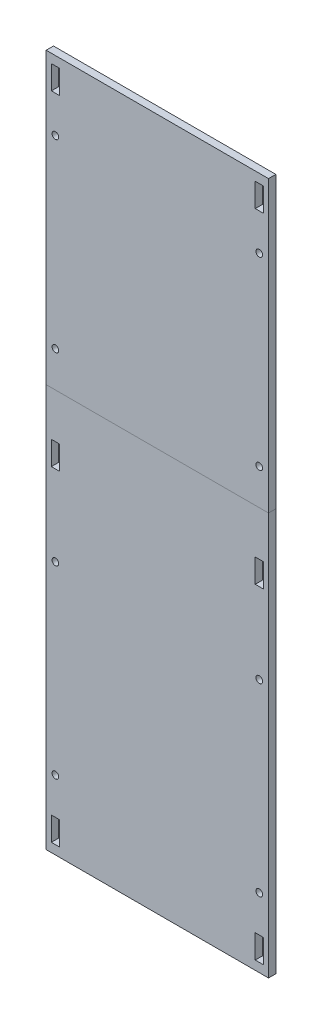
SolidWorks part; units mm, degrees
ref_plane "Front Plane" through (0, 0, 0) normal (0, 0, 1) x (1, 0, 0)
ref_plane "Top Plane" through (0, 0, 0) normal (0, 1, 0) x (1, 0, 0)
ref_plane "Right Plane" through (0, 0, 0) normal (1, 0, 0) x (0, 0, -1)
sketch "Sketch1" plane through (0, 0, 0) normal (0, 0, 1) x (1, 0, 0)
  line L2 (-44.17, -150) -> (-44.17, 150) construction
  line L4 (44.17, -150) -> (44.17, 150) construction
  line L5 (-44.17, -150) -> (44.17, 150) construction
  line L6 (-44.17, 150) -> (44.17, -150) construction
  line L7 (-48.17, -150) -> (48.17, -150)
  line L8 (-48.17, -150) -> (-48.17, 150)
  line L9 (-48.17, 150) -> (48.17, 150)
  line L10 (48.17, -150) -> (48.17, 150)
  line L11 (-48.17, -150) -> (48.17, 150) construction
  line L12 (-48.17, 150) -> (48.17, -150) construction
  line L13 (-45.9162, 135.875) -> (-42.4237, 135.875)
  line L14 (-45.9162, 135.875) -> (-45.9162, 146.125)
  line L15 (-45.9162, 146.125) -> (-42.4237, 146.125)
  line L16 (-42.4237, 135.875) -> (-42.4237, 146.125)
  line L17 (-45.9162, 135.875) -> (-42.4237, 146.125) construction
  line L18 (-45.9162, 146.125) -> (-42.4237, 135.875) construction
  line L19 (-45.9162, -5.125) -> (-42.4237, -5.125)
  line L20 (-45.9162, -5.125) -> (-45.9162, 5.125)
  line L21 (-45.9162, 5.125) -> (-42.4237, 5.125)
  line L22 (-42.4237, -5.125) -> (-42.4237, 5.125)
  line L23 (-45.9162, -5.125) -> (-42.4237, 5.125) construction
  line L24 (-45.9162, 5.125) -> (-42.4237, -5.125) construction
  line L25 (-45.9162, -146.125) -> (-42.4237, -146.125)
  line L26 (-45.9162, -146.125) -> (-45.9162, -135.875)
  line L27 (-45.9162, -135.875) -> (-42.4237, -135.875)
  line L28 (-42.4237, -146.125) -> (-42.4237, -135.875)
  line L29 (-45.9162, -146.125) -> (-42.4237, -135.875) construction
  line L30 (-45.9162, -135.875) -> (-42.4237, -146.125) construction
  circle A0 centre (-44.17, 120) radius 2.5 construction
  circle A1 centre (44.17, 120) radius 2.5 construction
  point P0 (0, 0)
  point P10 (-44.17, 141)
  point P12 (0, 0)
  point P20 (-44.17, 0)
  point P25 (-44.17, -141)
  dimension "D3" = 30
  dimension "D4" = 5
  dimension "D5" = 4
  dimension "D1" = 88.34
  dimension "D2" = 300
  dimension "D6" = 3.4925
  dimension "D7" = 10.25
  dimension "D8" = 9
  dimension "D9" = 9
extrude "Boss-Extrude1" add sketch "Sketch1" along normal mid plane 3.175 contours L9 L10 L7 L8
extrude "Cut-Extrude1" cut sketch "Sketch1<3>" against normal through all both and the other way through all contours L13 L16 L15 L14 | L19 L22 L21 L20 | L25 L28 L27 L26 region at (-44.17, 141, 0) region at (-44.17, 0, 0) region at (-44.17, -141, 0)
sketch "Sketch1<3>" plane through (0, 0, 0) normal (0, 0, 1) x (1, 0, 0) same geometry as "Sketch1"
sketch "Sketch2" plane through (0, 0, 1.5875) normal (0, 0, 1) x (1, 0, 0)
  point P0 (-44.17, 120)
hole_wizard "M2.5 Clearance Hole1" positions "Sketch2" profile "Sketch3" hole size "M2.5" standard "ANSI Metric" end condition through all
sketch "Sketch3" plane through (-44.17, 120, 1.5875) normal (1, 0, 0) x (0, -1, 0)
  line L0 (0, 0) -> (0, 3.175)
  line L1 (0, 3.175) -> (1.45, 3.175)
  line L2 (1.45, 3.175) -> (1.45, 0)
  line L5 (1.45, 0) -> (0, 0)
  line L11 (0, -6.35) -> (0, 107.95) construction
  dimension "Thru Hole Dia." = 2.9
  dimension "Thru Hole Depth" = 3.175
pattern_linear "LPattern1" count 4 spacing 80 along (0, -1, 0) of "M2.5 Clearance Hole1"
mirror "Mirror1" about plane through (0, 0, 0) normal (1, 0, 0) of "LPattern1", "Cut-Extrude1"
ref_plane "Plane1" through (0, 24.5, 0) normal (0, 1, 0) x (1, 0, 0)
split "Split1" trim tools "Plane1" bodies to split 105 resulting bodies 108 109
